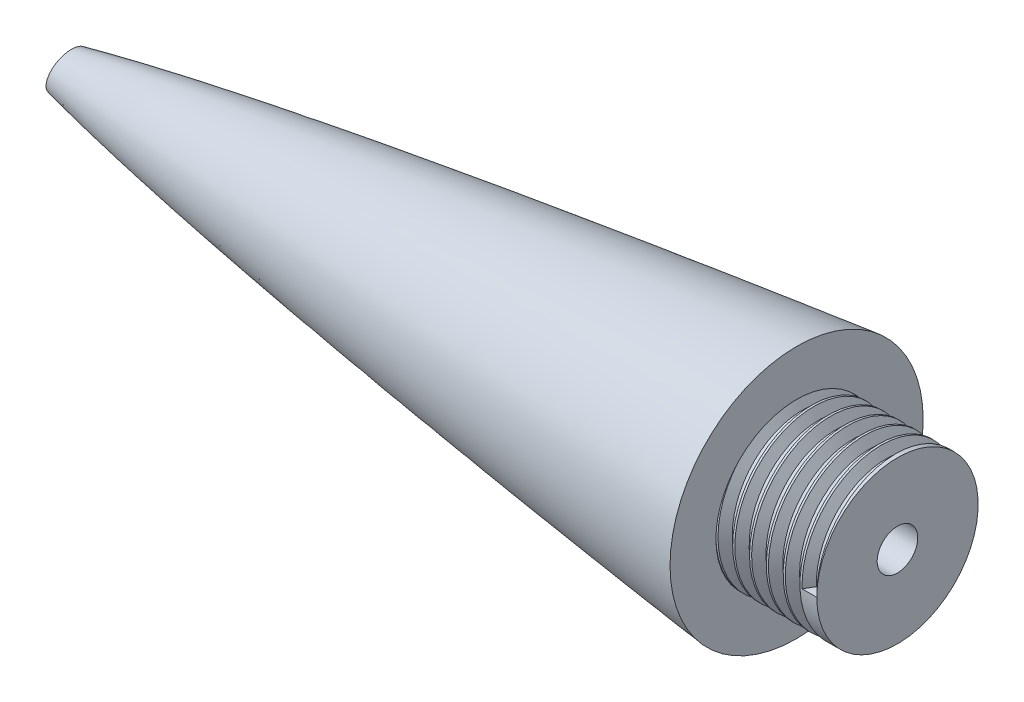
SolidWorks part; units mm, degrees
ref_plane "Front Plane" through (0, 0, 0) normal (0, 0, 1) x (1, 0, 0)
ref_plane "Top Plane" through (0, 0, 0) normal (0, 1, 0) x (1, 0, 0)
ref_plane "Right Plane" through (0, 0, 0) normal (1, 0, 0) x (0, 0, -1)
sketch "Sketch1" plane through (0, 0, 0) normal (0, 0, 1) x (1, 0, 0)
  line L6 (0.0514, -0.1338) -> (113.1882, -0.1338)
  line L8 (100.4882, 10.0262) -> (113.1882, 10.0262)
  line L9 (113.1882, 10.0262) -> (113.1882, -0.1338)
  line L10 (100.4882, 15.8047) -> (100.4882, 10.0262)
  spline S5 degree 4 poles (0.0514, -0.1338) (0.0552, -0.1267) (0.0638, -0.1134) (0.0864, -0.0909) (0.124, -0.0613) (0.1696, -0.0296) (0.2373, 0.0121) (0.3206, 0.0586) (0.444, 0.1217) (0.609, 0.1982) (0.8023, 0.2808) (1.0241, 0.3689) (1.2674, 0.4603) (1.5321, 0.5547) (1.9669, 0.7026) (2.7462, 0.9493) (4.169, 1.3583) (6.8533, 2.0434) (11.8366, 3.1571) (21.2787, 4.9817) (38.2766, 7.7916) (66.0855, 11.7234) (103.546, 16.2897) (148.3227, 21.1103) (197.0023, 25.8223) (245.7188, 30.1326) (294.4636, 34.1082) (343.2313, 37.7909) (392.0185, 41.2062) (440.8227, 44.3696) (489.642, 47.2884) (538.4754, 49.9634) (587.3218, 52.3879) (636.1808, 54.5467) (678.943, 56.179) (715.6038, 57.3637) (745.2557, 58.1525) (765.2912, 58.5863) (781.8204, 58.8601) (792.2379, 58.9748) (797.4469, 59.0114) (800.0514, 59.0162) knots 0 0 0 0 0 0.00004 0.000079 0.000158 0.000237 0.000317 0.000475 0.000633 0.000928 0.001222 0.001522 0.001822 0.002222 0.002622 0.00381 0.005894 0.009596 0.016421 0.029243 0.053793 0.095411 0.156318 0.217224 0.278131 0.339037 0.399944 0.46085 0.521757 0.582663 0.64357 0.704476 0.765383 0.826289 0.887196 0.917649 0.948102 0.974051 0.987026 1 1 1 1 1 construction
  spline S6 degree 4 poles (0.0514, -0.1338) (0.0552, -0.1267) (0.0638, -0.1134) (0.0864, -0.0909) (0.124, -0.0613) (0.1696, -0.0296) (0.2373, 0.0121) (0.3206, 0.0586) (0.444, 0.1217) (0.609, 0.1982) (0.8023, 0.2808) (1.0241, 0.3689) (1.2674, 0.4603) (1.5321, 0.5547) (1.9669, 0.7026) (2.7462, 0.9493) (4.169, 1.3583) (6.8533, 2.0434) (11.8366, 3.1571) (21.2787, 4.9817) (38.2766, 7.7916) (60.2248, 10.8948) (79.6614, 13.3517) (94.222, 15.0794) (100.4882, 15.8047) knots 0 0 0 0 0 0.00004 0.000079 0.000158 0.000237 0.000317 0.000475 0.000633 0.000928 0.001222 0.001522 0.001822 0.002222 0.002622 0.00381 0.005894 0.009596 0.016421 0.029243 0.053793 0.095411 0.126835 0.126835 0.126835 0.126835 0.126835
  dimension "D1" = 113.1368
  dimension "D3" = 10.16
  dimension "D4" = 12.7
  dimension "D2" = 15.9385
revolve "Revolve1" add sketch "Sketch1" angle 360 about L6 region at (69.1242, 5.4042, 0)
hole_wizard "1/4-20 Tapped Hole1" positions "Sketch4" profile "Sketch6" tap size "1/4-20" standard "ANSI Inch" end condition through all
sketch "Sketch4" plane through (113.1882, 0, 0) normal (1, 0, 0) x (0, 0, -1)
  point P0 (0, 0)
cosmetic thread "Hole Thread1"
sketch "Sketch6" plane through (113.1882, 0, 0) normal (0, 1, 0) x (0, 0, -1)
  line L0 (0, 0) -> (0, 113.1368)
  line L1 (0, 113.1368) -> (2.5527, 113.1368)
  line L2 (2.5527, 113.1368) -> (2.5527, 0)
  line L5 (2.5527, 0) -> (0, 0)
  line L11 (0, -6.35) -> (0, 107.95) construction
  dimension "Thru Tap Drill Dia." = 5.1054
  dimension "Thru Tap Drill Depth" = 113.1368
thread "Thread1" pitch 2.1167 method cut profile "Thread Profile1" start angle 0, offset 0, length 0, pitch 2.1167, diameter 20.32
ref_plane "Plane1" through (113.1882, -0.1338, 10.16) normal (0, -1, 0) x (0, 0, 1)
sketch "Thread Profile1" plane through (113.1882, -0.1338, 10.16) normal (0, -1, 0) x (0, 0, 1)
  line L0 (0, 0) -> (0, 2.1167) construction
  line L11 (0, 0) -> (0, 1.8521)
  line L12 (0, 1.8521) -> (-1.1457, 1.1906)
  line L13 (-1.1457, 1.1906) -> (-1.1457, 0.6615)
  line L15 (-1.1457, 0.6615) -> (0, 0)
  line L17 (-1.1457, 0.926) -> (0, 0.926) construction
  point P2 (0, 0)
  dimension "Pitch" = 2.1167
  dimension "Profile_Angle" = 60
  dimension "Profile_Land" = 0.5292
  dimension "Profile_Height" = 1.1457
